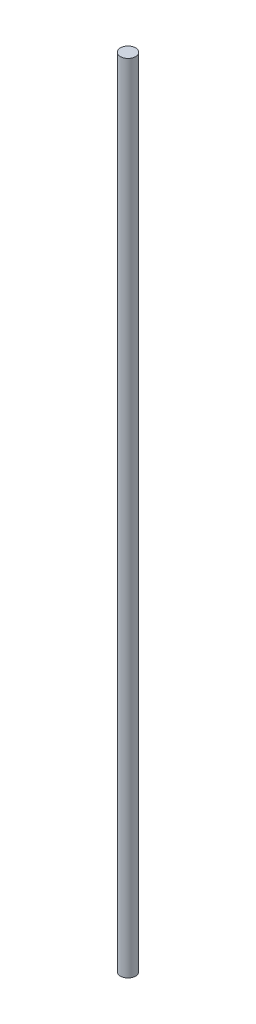
SolidWorks part; units mm, degrees
material "1060 Alloy"
ref_plane "Front Plane" through (0, 0, 0) normal (0, 0, 1) x (1, 0, 0)
ref_plane "Top Plane" through (0, 0, 0) normal (0, 1, 0) x (1, 0, 0)
ref_plane "Right Plane" through (0, 0, 0) normal (1, 0, 0) x (0, 0, -1)
sketch "Sketch1" plane through (0, 0, 0) normal (0, 1, 0) x (1, 0, 0)
  circle A0 centre (0, 0) radius 5
  dimension "D1" = 10
extrude "Boss-Extrude1" add sketch "Sketch1" along normal blind 524
equation "\"D1@Boss-Extrude1\"=450+74"
